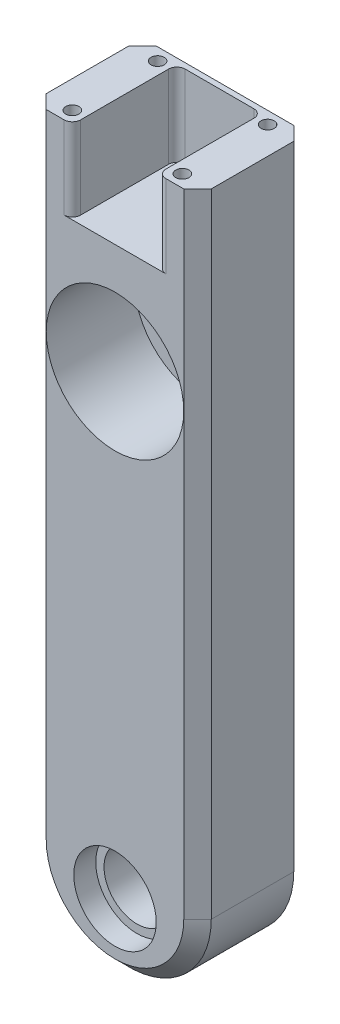
SolidWorks part; units mm, degrees
ref_plane "Front Plane" through (0, 0, 0) normal (0, 0, 1) x (1, 0, 0)
ref_plane "Top Plane" through (0, 0, 0) normal (0, 1, 0) x (1, 0, 0)
ref_plane "Right Plane" through (0, 0, 0) normal (1, 0, 0) x (0, 0, -1)
sketch "Sketch1" plane through (0, 0, 0) normal (0, 0, 1) x (1, 0, 0)
  line L1 (-15, -80) -> (-15, 20)
  line L2 (15, -80) -> (15, 20)
  line L6 (15, 20) -> (-15, 20)
  arc A0 (-15, -80) -> (15, -80) centre (0, -80) ccw
  circle A3 centre (0, 0) radius 4
  circle A4 centre (0, -83) radius 7.5
  point P2 (0, 0)
  point P7 (0, -83.4706)
  dimension "D3" = 15
  dimension "D4" = 8
  dimension "D5" = 20
  dimension "D1" = 30
  dimension "D2" = 100
  dimension "D6" = 15
  dimension "D7" = 3
extrude "Boss-Extrude1" add sketch "Sketch1" along normal mid plane 20 contours L1 A0 L2 L6 A3 region at (0, -33.8585, 0)
sketch "Sketch2" plane through (0, 0, 0) normal (0, 0, 1) x (1, 0, 0)
  circle A2 centre (0, -83) radius 6
  circle A3 centre (0, -83) radius 7.5
  point P0 (0, -82.5)
  point P1 (2.3, -75)
  point P5 (2.3, -75)
  point P6 (2.3, -75)
  point P7 (0, -80)
  point P11 (0, 0)
  dimension "D1" = 12
extrude "Boss-Extrude2" add sketch "Sketch2" along normal mid plane 12 contours A3 A2 region at (-7.2879, -83, 0)
sketch "Sketch11" plane through (0, 0, -10) normal (0, 0, -1) x (-1, 0, 0)
  line L0 (0, 0) -> (0, 23.3498) construction
  line L1 (0, 6) -> (-5.1962, 3)
  line L2 (-5.1962, 3) -> (-5.1962, -3)
  line L3 (-5.1962, -3) -> (0, -6)
  line L4 (0, -6) -> (5.1962, -3)
  line L5 (5.1962, -3) -> (5.1962, 3)
  line L6 (5.1962, 3) -> (0, 6)
  circle A0 centre (0, 0) radius 5.1962 construction
  dimension "D1" = 6
extrude "Cut-Extrude2" cut sketch "Sketch11" against normal blind 6
sketch "Sketch4" plane through (0, 0, 10) normal (0, 0, -1) x (-1, 0, 0)
  circle A1 centre (0, 0) radius 12.5
  dimension "D1" = 25
extrude "Cut-Extrude1" cut sketch "Sketch4" along normal blind 16
sketch "Sketch8" plane through (0, 20, 0) normal (0, 1, 0) x (1, 0, 0)
  line L0 (0, 0) -> (0, 11.5319) construction
  line L1 (0, 0) -> (18.5024, 0) construction
  line L2 (15, -10) -> (-15, -10) construction
  line L3 (-15, 10) -> (-7.75, 10)
  line L4 (-15, 10) -> (-15, -10)
  line L5 (-15, -10) -> (-7.75, -10)
  line L6 (-7.75, 10) -> (-7.75, -10)
  line L8 (15, 10) -> (7.75, 10)
  line L9 (15, 10) -> (15, -10)
  line L10 (15, -10) -> (7.75, -10)
  line L11 (7.75, 10) -> (7.75, -10)
  circle A0 centre (-10, -7.75) radius 1.2
  circle A1 centre (-10, 7.75) radius 1.2
  circle A2 centre (10, -7.75) radius 1.2
  circle A3 centre (10, 7.75) radius 1.2
  dimension "D1" = 2.4
  dimension "D3" = 15.5
  dimension "D4" = 7.75
  dimension "D2" = 10
  dimension "D5" = 15.5
extrude "Boss-Extrude3" add sketch "Sketch8" along normal blind 15
sketch "Sketch10" plane through (0, 20, 0) normal (0, 1, 0) x (1, 0, 0)
  line L0 (7.75, 10) -> (-7.75, 10) construction
  line L1 (7.75, 10) -> (-7.75, 10)
  line L2 (7.75, 10) -> (7.75, -10) construction
  line L3 (-7.75, -10) -> (-7.75, 10) construction
  line L4 (7.75, 10) -> (7.75, 9)
  line L5 (-7.75, 9) -> (-7.75, 10)
  line L6 (-7.75, 9) -> (7.75, 9)
  dimension "D1" = 1
extrude "Boss-Extrude4" add sketch "Sketch10" along normal up to surface (15 mm away) up to face at (11.375, 35, 0)
fillet "Fillet1" radius 1.5 4 edges at (-7.75, 27.5, 10) (7.75, 27.5, 10) (7.75, 27.5, -9) (-7.75, 27.5, -9)
chamfer "Chamfer1" distance 2.5 angle 45 6 edges at (15, -22.5, 10) (0, -95, 10) (-15, -22.5, 10) (15, -22.5, -10) (0, -95, -10) (-15, -22.5, -10)
